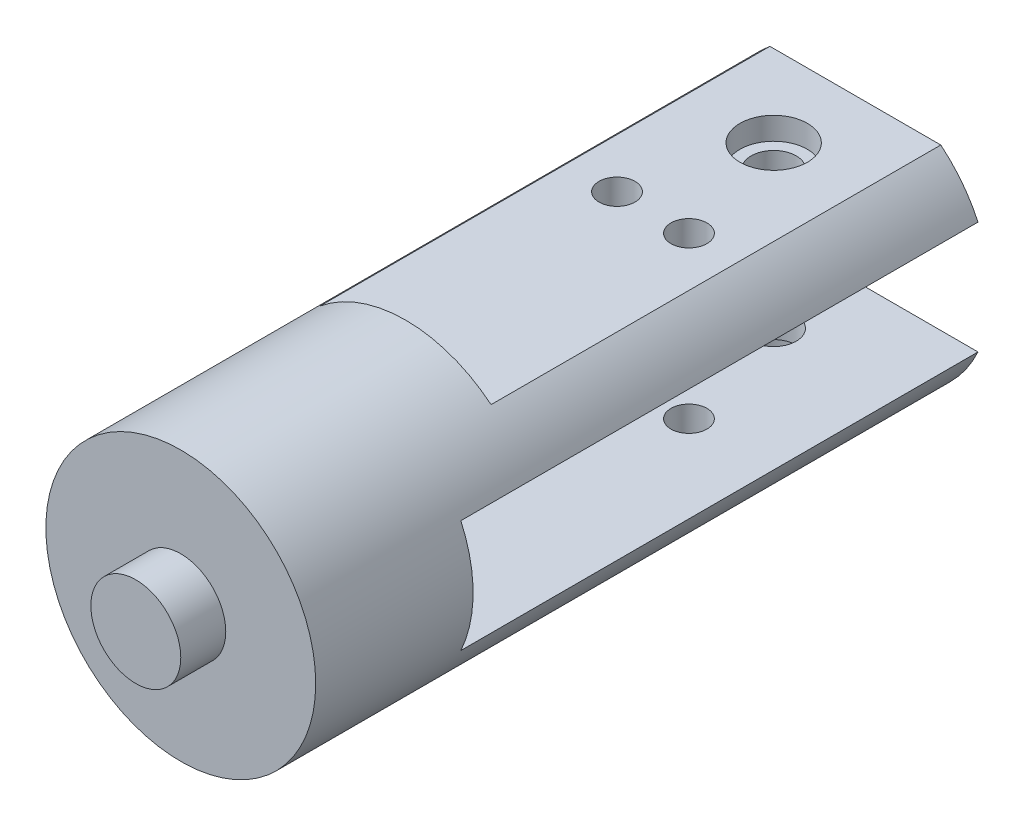
SolidWorks part; units mm, degrees
ref_plane "Ön Düzlem" through (0, 0, 0) normal (0, 0, 1) x (1, 0, 0)
ref_plane "Üst Düzlem" through (0, 0, 0) normal (0, 1, 0) x (1, 0, 0)
ref_plane "Sağ Düzlem" through (0, 0, 0) normal (1, 0, 0) x (0, 0, -1)
sketch "Çizim1" plane through (0, 0, 0) normal (0, 0, 1) x (1, 0, 0)
  circle A0 centre (0, 0) radius 30
  circle A1 centre (0, 0) radius 10
  dimension "D1" = 60
  dimension "D2" = 20
extrude "Yükseklik-Ekstrüzyon2" add sketch "Çizim1" along normal blind 25 contours A0 A1 | A1 region at (-29.1515, 0, 0) region at (0, 0, 0)
extrude "Yükseklik-Ekstrüzyon3" add sketch "Çizim1<4>" along normal blind 35 contours A1 region at (0, 0, 0)
sketch "Çizim1<4>" plane through (0, 0, 0) normal (0, 0, 1) x (1, 0, 0) same geometry as "Çizim1"
extrude "Yükseklik-Ekstrüzyon4" add sketch "Çizim1<5>" against normal blind 125 contours A0 A1 | A1 region at (-29.1515, 0, 0) region at (0, 0, 0)
sketch "Çizim1<5>" plane through (0, 0, 0) normal (0, 0, 1) x (1, 0, 0) same geometry as "Çizim1"
sketch "Çizim3" plane through (0, 0, -125) normal (0, 0, -1) x (-1, 0, 0)
  line L0 (-27.2718, 12.5) -> (-27.2718, -12.5)
  line L1 (-27.2718, 12.5) -> (27.2718, 12.5)
  line L2 (-27.2718, 12.5) -> (-27.2718, -12.5)
  line L3 (-27.2718, -12.5) -> (27.2718, -12.5)
  line L4 (27.2718, 12.5) -> (27.2718, -12.5)
  line L5 (-27.2718, 12.5) -> (27.2718, -12.5) construction
  line L6 (-27.2718, -12.5) -> (27.2718, 12.5) construction
  line L7 (27.2718, 12.5) -> (27.2718, -12.5)
  circle A0 centre (0, 0) radius 30 construction
  arc A1 (-27.2718, 12.5) -> (-27.2718, -12.5) centre (0, 0) ccw
  arc A2 (27.2718, 12.5) -> (27.2718, -12.5) centre (0, 0) cw
  point P0 (0, 0)
  circle M5 centre (0, 0) radius 30
  dimension "D1" = 25
extrude "Kes-Ekstrüzyon1" cut sketch "Çizim3" against normal blind 115 contours L0 M5 | L4 M5 | L2 L1 L4 L3 region at (28.3674, 0, -125) region at (-28.3674, 0, -125)
sketch "Çizim4" plane through (0, 0, -125) normal (0, 0, -1) x (-1, 0, 0)
  line L0 (-19, 23.2164) -> (19, 23.2164)
  line L1 (0, 23.2164) -> (0, 0) construction
  line L2 (-30, 0) -> (30, 0) construction
  line L3 (-19, -23.2164) -> (19, -23.2164)
  arc A0 (27.2718, 12.5) -> (-27.2718, 12.5) centre (0, 0) ccw construction
  arc A1 (-27.2718, 12.5) -> (-27.2718, -12.5) centre (0, 0) ccw construction
  arc A2 (27.2718, -12.5) -> (27.2718, 12.5) centre (0, 0) ccw construction
  arc A3 (-19, 23.2164) -> (19, 23.2164) centre (0, 0) cw
  arc A4 (-19, -23.2164) -> (19, -23.2164) centre (0, 0) ccw
  dimension "D1" = 38
extrude "Kes-Ekstrüzyon2" cut sketch "Çizim4" against normal blind 100
sketch "Çizim5" plane through (0, 23.2164, 0) normal (0, 1, 0) x (1, 0, 0)
  line L0 (-19, 25) -> (-19, 125) construction
  line L1 (19, 25) -> (19, 125) construction
  line L2 (19, 125) -> (-19, 125) construction
  circle A0 centre (-8, 80) radius 4
  circle A1 centre (8, 80) radius 4
  dimension "D1" = 8
  dimension "D2" = 11
  dimension "D3" = 11
  dimension "D4" = 45
extrude "Kes-Ekstrüzyon3" cut sketch "Çizim5" against normal blind 100
sketch "Çizim6" plane through (0, 23.2164, 0) normal (0, 1, 0) x (1, 0, 0)
  line L0 (0, 125) -> (0, 71.1384) construction
  line L1 (19, 125) -> (-19, 125) construction
  circle A0 centre (0, 106.843) radius 7.5
  circle A1 centre (0, 106.843) radius 5
  dimension "D1" = 15
  dimension "D2" = 10
extrude "Kes-Ekstrüzyon4" cut sketch "Çizim6" against normal blind 5 contours L0 A1 | A1 L0 | L0 A0 A1 | A0 L0 A1 region at (5.1847, 23.2164, -112.0277) region at (-0.1677, 23.2164, -113.093) region at (2.1221, 23.2164, -106.843) region at (-2.1221, 23.2164, -106.843)
extrude "Kes-Ekstrüzyon5" cut sketch "Çizim6<3>" against normal up to surface (10.7164 mm away) contours L0 A1 | A1 L0 region at (2.1221, 23.2164, -106.843) region at (-2.1221, 23.2164, -106.843) up to face at (-8, 12.5, -84)
sketch "Çizim6<3>" plane through (0, 23.2164, 0) normal (0, 1, 0) x (1, 0, 0) same geometry as "Çizim6"
mirror "Aynalama1" about plane through (0, 0, 0) normal (0, 1, 0) of "Kes-Ekstrüzyon5", "Kes-Ekstrüzyon4"
scale "Ölçek1" bodies to scale 110 scale about centroid uniform scaling yes scale factor 0.2
